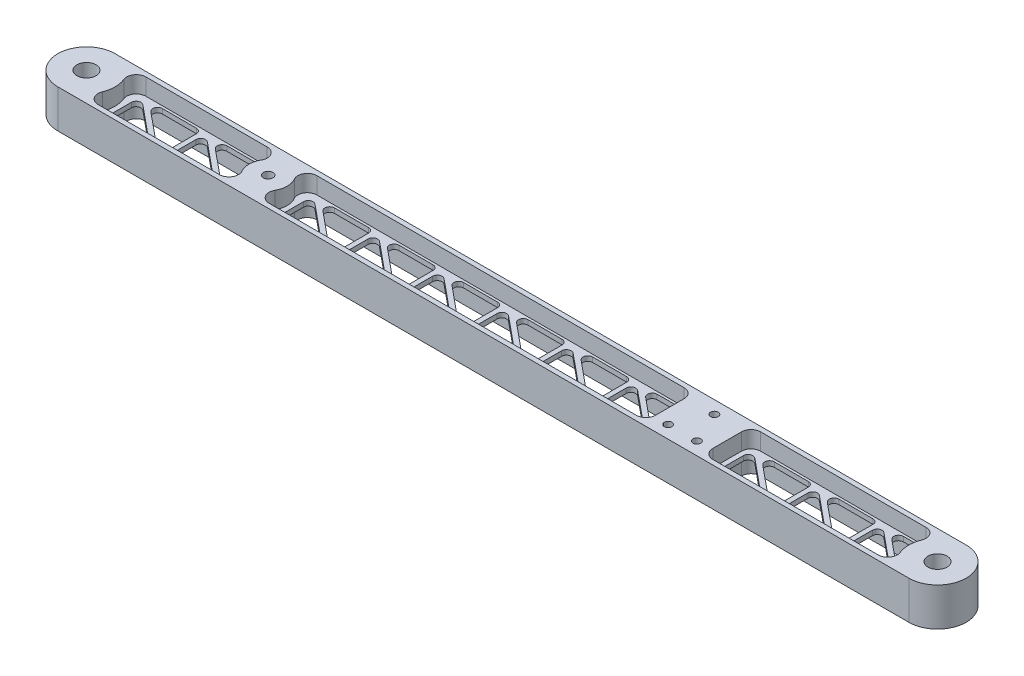
SolidWorks part; units mm, degrees
note: The reader was unsure of these and kept them because the rebuilt part matched: shared geometry of "Sketch13<4>".
material "7075-T6 (SN)"
ref_plane "Front Plane" through (0, 0, 0) normal (0, 0, 1) x (1, 0, 0)
ref_plane "Top Plane" through (0, 0, 0) normal (0, 1, 0) x (1, 0, 0)
ref_plane "Right Plane" through (0, 0, 0) normal (1, 0, 0) x (0, 0, -1)
sketch "Sketch2" plane through (0, 0, 0) normal (0, 1, 0) x (1, 0, 0)
  line L0 (0, 0) -> (120.65, 0)
  line L1 (0, 0) -> (565.15, 0)
  line L2 (0, 0) -> (0, 38.1) construction
  line L3 (0, 38.1) -> (565.15, 38.1)
  line L4 (565.15, 0) -> (565.15, 38.1) construction
  line L5 (120.65, 0) -> (120.65, 38.1) construction
  circle A0 centre (120.65, 19.05) radius 19.05
  arc A1 (565.15, 38.1) -> (565.15, 0) centre (565.15, 19.05) cw
  circle A2 centre (120.65, 19.05) radius 3.175
  circle A3 centre (565.15, 19.05) radius 6.35
  arc A4 (0, 38.1) -> (0, 0) centre (0, 19.05) ccw
  circle A5 centre (0, 19.05) radius 6.35
  dimension "D4" = 6.35
  dimension "D5" = 12.7
  dimension "D6" = 12.7
  dimension "D1" = 565.15
  dimension "D2" = 38.1
  dimension "D3" = 120.65
extrude "Boss-Extrude1" add sketch "Sketch2" along normal blind 25.4 contours A0 L3 L2 L0 | A0 A2 | A1 L3 A0 L1 A3
sketch "Sketch12" plane through (0, 0, -38.1) normal (0, 0, -1) x (-1, 0, 0)
  line L0 (-565.15, 25.4) -> (-425.45, 25.4)
  line L1 (0, 25.4) -> (-565.15, 25.4) construction
  line L2 (-387.35, 0) -> (-425.45, 0)
  line L3 (-425.45, 25.4) -> (-425.45, 0)
  line L5 (-387.35, 0) -> (-387.35, 25.4)
  line L6 (-425.45, 25.4) -> (-387.35, 25.4)
  line L7 (0, 0) -> (-565.15, 0) construction
  dimension "D1" = 139.7
  dimension "D2" = 38.1
sketch "Sketch13" plane through (0, 25.4, 0) normal (0, 1, 0) x (1, 0, 0)
  line L0 (565.15, 38.1) -> (565.15, 0) construction
  line L1 (0, 38.1) -> (0, 0) construction
  line L2 (565.15, 38.1) -> (565.15, 0) construction
  line L3 (565.15, 34.925) -> (0, 34.925)
  line L4 (0, 3.175) -> (565.15, 3.175)
  line L5 (565.15, 38.1) -> (425.45, 38.1) construction
  line L6 (0, 0) -> (565.15, 0) construction
  line L7 (19.05, 19.05) -> (22.225, 19.05) construction
  line L8 (22.225, 33.3375) -> (22.225, 4.7625)
  line L9 (22.225, 4.7625) -> (56.9185, 4.7625)
  line L10 (56.9185, 4.7625) -> (22.225, 33.3375)
  line L11 (27.219, 33.3375) -> (61.9125, 4.7625)
  line L12 (61.9125, 4.7625) -> (61.9125, 33.3375)
  line L13 (61.9125, 33.3375) -> (27.219, 33.3375)
  line L14 (65.0875, 33.3375) -> (65.0875, 4.7625)
  line L15 (65.0875, 4.7625) -> (99.781, 4.7625)
  line L16 (99.781, 4.7625) -> (65.0875, 33.3375)
  line L17 (70.0815, 33.3375) -> (104.775, 4.7625)
  line L18 (104.775, 4.7625) -> (104.775, 33.3375)
  line L19 (104.775, 33.3375) -> (70.0815, 33.3375)
  line L20 (61.9125, 19.05) -> (65.0875, 19.05) construction
  line L21 (350.8375, 33.3375) -> (350.8375, 4.7625)
  line L22 (350.8375, 4.7625) -> (384.175, 4.7625)
  line L23 (44.5658, 33.3375) -> (44.5658, 34.925) construction
  line L24 (39.5717, 4.7625) -> (39.5717, 3.175) construction
  line L25 (120.65, 34.925) -> (120.65, 3.175) construction
  line L26 (384.175, 5.8793) -> (350.8375, 33.3375)
  line L27 (355.8315, 33.3375) -> (384.175, 9.9926)
  line L28 (107.95, 19.05) -> (104.775, 19.05) construction
  line L29 (133.35, 19.05) -> (136.525, 19.05) construction
  line L30 (136.525, 33.3375) -> (136.525, 4.7625)
  line L31 (136.525, 4.7625) -> (171.2185, 4.7625)
  line L32 (171.2185, 4.7625) -> (136.525, 33.3375)
  line L33 (141.519, 33.3375) -> (176.2125, 4.7625)
  line L34 (176.2125, 4.7625) -> (176.2125, 33.3375)
  line L35 (176.2125, 33.3375) -> (141.519, 33.3375)
  line L36 (387.35, 38.1) -> (387.35, 0)
  line L37 (425.45, 38.1) -> (387.35, 38.1) construction
  line L38 (387.35, 0) -> (425.45, 0)
  line L39 (425.45, 0) -> (425.45, 38.1)
  line L40 (387.35, 38.1) -> (425.45, 38.1) construction
  line L41 (425.45, 38.1) -> (387.35, 38.1)
  line L42 (179.3875, 33.3375) -> (179.3875, 4.7625)
  line L43 (179.3875, 4.7625) -> (214.081, 4.7625)
  line L44 (214.081, 4.7625) -> (179.3875, 33.3375)
  line L45 (184.3815, 33.3375) -> (219.075, 4.7625)
  line L46 (219.075, 4.7625) -> (219.075, 33.3375)
  line L47 (219.075, 33.3375) -> (184.3815, 33.3375)
  line L48 (176.2125, 19.05) -> (179.3875, 19.05) construction
  line L49 (222.25, 33.3375) -> (222.25, 4.7625)
  line L50 (222.25, 4.7625) -> (256.9435, 4.7625)
  line L51 (256.9435, 4.7625) -> (222.25, 33.3375)
  line L52 (227.244, 33.3375) -> (261.9375, 4.7625)
  line L53 (261.9375, 4.7625) -> (261.9375, 33.3375)
  line L54 (261.9375, 33.3375) -> (227.244, 33.3375)
  line L55 (219.075, 19.05) -> (222.25, 19.05) construction
  line L56 (265.1125, 33.3375) -> (265.1125, 4.7625)
  line L57 (265.1125, 4.7625) -> (299.806, 4.7625)
  line L58 (299.806, 4.7625) -> (265.1125, 33.3375)
  line L59 (270.1065, 33.3375) -> (304.8, 4.7625)
  line L60 (304.8, 4.7625) -> (304.8, 33.3375)
  line L61 (304.8, 33.3375) -> (270.1065, 33.3375)
  line L62 (261.9375, 19.05) -> (265.1125, 19.05) construction
  line L63 (307.975, 33.3375) -> (307.975, 4.7625)
  line L64 (307.975, 4.7625) -> (342.6685, 4.7625)
  line L65 (342.6685, 4.7625) -> (307.975, 33.3375)
  line L66 (312.969, 33.3375) -> (347.6625, 4.7625)
  line L67 (347.6625, 4.7625) -> (347.6625, 33.3375)
  line L68 (347.6625, 33.3375) -> (312.969, 33.3375)
  line L69 (304.8, 19.05) -> (307.975, 19.05) construction
  line L70 (548.126, 33.3375) -> (519.344, 33.3375)
  line L71 (530.4996, 20.036) -> (532.5181, 22.4868) construction
  line L72 (546.6492, 6.7345) -> (514.35, 33.3375)
  line L73 (384.175, 5.8793) -> (384.175, 4.7625)
  line L75 (384.175, 5.8793) -> (350.8375, 33.3375)
  line L76 (384.175, 33.3375) -> (355.8315, 33.3375)
  line L77 (347.6625, 19.05) -> (350.8375, 19.05) construction
  line L78 (384.175, 33.3375) -> (384.175, 9.9926)
  line L84 (425.45, 19.05) -> (428.625, 19.05) construction
  line L85 (428.625, 33.3375) -> (428.625, 4.7625)
  line L86 (428.625, 4.7625) -> (463.3185, 4.7625)
  line L87 (463.3185, 4.7625) -> (428.625, 33.3375)
  line L88 (433.619, 33.3375) -> (468.3125, 4.7625)
  line L89 (468.3125, 4.7625) -> (468.3125, 33.3375)
  line L90 (468.3125, 33.3375) -> (433.619, 33.3375)
  line L91 (471.4875, 33.3375) -> (471.4875, 4.7625)
  line L92 (471.4875, 4.7625) -> (506.181, 4.7625)
  line L93 (506.181, 4.7625) -> (471.4875, 33.3375)
  line L94 (476.4815, 33.3375) -> (511.175, 4.7625)
  line L95 (511.175, 4.7625) -> (511.175, 33.3375)
  line L96 (511.175, 33.3375) -> (476.4815, 33.3375)
  line L97 (468.3125, 19.05) -> (471.4875, 19.05) construction
  line L98 (514.35, 33.3375) -> (514.35, 4.7625)
  line L99 (514.35, 4.7625) -> (548.126, 4.7625)
  line L101 (519.344, 33.3375) -> (543.6845, 13.2897)
  line L104 (511.175, 19.05) -> (514.35, 19.05) construction
  line L112 (387.35, 19.05) -> (425.45, 19.05) construction
  line L113 (565.15, 19.05) -> (546.1, 19.05) construction
  line L114 (546.1, 19.05) -> (546.1, 38.1) construction
  line L115 (546.1, 38.1) -> (546.1, 3.175) construction
  line L116 (406.4, 38.1) -> (406.4, 0) construction
  line L117 (396.875, 38.1) -> (396.875, 0) construction
  line L118 (415.925, 0) -> (415.925, 38.1) construction
  line L119 (387.35, 29.6333) -> (425.45, 29.6333) construction
  line L120 (387.35, 8.4667) -> (425.45, 8.4667) construction
  line L121 (568.4516, 33.3375) -> (565.15, 33.3375) [skipped]
  line L122 (554.0375, 4.7625) -> (554.0375, 33.3375) [skipped]
  line L123 (554.8268, -0.0009) -> (549.9493, 4.0164) [skipped]
  line L124 (390.525, 29.6333) -> (390.525, 33.3375) [skipped]
  circle A0 centre (565.15, 19.05) radius 19.05
  arc A1 (109.6515, 25.4) -> (109.6515, 12.7) centre (120.65, 19.05) ccw
  circle A2 centre (0, 19.05) radius 19.05
  arc A3 (104.1522, 34.925) -> (109.6515, 25.4) centre (104.1522, 28.575) cw
  arc A4 (546.6492, 6.7345) -> (548.126, 4.7625) centre (565.15, 19.05) ccw
  arc A5 (548.126, 33.3375) -> (543.6845, 13.2897) centre (565.15, 19.05) ccw
  arc A6 (109.6515, 12.7) -> (104.1522, 3.175) centre (104.1522, 9.525) cw
  arc A7 (131.6485, 12.7) -> (137.1478, 3.175) centre (137.1478, 9.525) ccw
  arc A8 (137.1478, 34.925) -> (131.6485, 25.4) centre (137.1478, 28.575) ccw
  arc A9 (131.6485, 12.7) -> (131.6485, 25.4) centre (120.65, 19.05) ccw
  point P164 (406.4, 29.6333)
  dimension "D1" = 25.4
  dimension "D9" = 3.175
  dimension "D30" = 8.4667
  dimension "D31" = 3.175
  dimension "D19" = 3.175
  dimension "D25" = 3.175
  dimension "D4" = 6.35
  dimension "D2" = 3.175
  dimension "D3" = 3.175
  dimension "Triangle Size" = 1.5875
  dimension "D6" = 3.175
  dimension "D7" = 3.175
  dimension "D10" = 3.175
  dimension "D11" = 3.175
  dimension "D14" = 3.175
  dimension "D15" = 139.7
  dimension "D16" = 38.1
  dimension "D17" = 6
  dimension "D18" = 3.175
  dimension "D20" = 3.175
  dimension "D23" = 3.175
  dimension "D26" = 3.175
  dimension "D27" = 9.525
  dimension "D28" = 9.525
  dimension "D29" = 8.4667
  dimension "D8" = 2
  dimension "D24" = 3
extrude "Cut-Extrude2" cut sketch "Sketch13" against normal up to next
extrude "Cut-Extrude3" cut sketch "Sketch13<4>" against normal blind 11.1125
sketch "Sketch13<4>" plane through (0, 25.4, 0) normal (0, 1, 0) x (1, 0, 0) same geometry as "Sketch13"
ref_plane "Plane1" through (0, 12.7, 0) normal (0, -1, 0) x (-1, 0, 0)
mirror "Mirror1" about plane through (0, 12.7, 0) normal (0, -1, 0) of "Cut-Extrude3"
fillet "Fillet1" radius 3.175 63 edges at (104.775, 12.7, -33.3375) (104.775, 12.7, -4.7625) (70.0815, 12.7, -33.3375) (99.781, 12.7, -4.7625) (65.0875, 12.7, -4.7625) (65.0875, 12.7, -33.3375) (61.9125, 12.7, -33.3375) (61.9125, 12.7, -4.7625) (27.219, 12.7, -33.3375) (56.9185, 12.7, -4.7625) (22.225, 12.7, -4.7625) (22.225, 12.7, -33.3375) (347.6625, 12.7, -33.3375) (347.6625, 12.7, -4.7625) (312.969, 12.7, -33.3375) (342.6685, 12.7, -4.7625) (307.975, 12.7, -4.7625) (307.975, 12.7, -33.3375) (304.8, 12.7, -33.3375) (304.8, 12.7, -4.7625) (270.1065, 12.7, -33.3375) (299.806, 12.7, -4.7625) (265.1125, 12.7, -4.7625) (265.1125, 12.7, -33.3375) (261.9375, 12.7, -33.3375) (261.9375, 12.7, -4.7625) (227.244, 12.7, -33.3375) (256.9435, 12.7, -4.7625) (222.25, 12.7, -4.7625) (222.25, 12.7, -33.3375) (219.075, 12.7, -33.3375) (219.075, 12.7, -4.7625) (184.3815, 12.7, -33.3375) (214.081, 12.7, -4.7625) (179.3875, 12.7, -4.7625) (179.3875, 12.7, -33.3375) (176.2125, 12.7, -33.3375) (176.2125, 12.7, -4.7625) (141.519, 12.7, -33.3375) (171.2185, 12.7, -4.7625) (136.525, 12.7, -4.7625) (136.525, 12.7, -33.3375) (514.35, 12.7, -4.7625) (511.175, 12.7, -33.3375) (511.175, 12.7, -4.7625) (476.4815, 12.7, -33.3375) (506.181, 12.7, -4.7625) (471.4875, 12.7, -4.7625) (471.4875, 12.7, -33.3375) (468.3125, 12.7, -33.3375) (468.3125, 12.7, -4.7625) (433.619, 12.7, -33.3375) (463.3185, 12.7, -4.7625) (428.625, 12.7, -4.7625) (428.625, 12.7, -33.3375) (548.126, 12.7, -33.3375) (543.6845, 12.7, -13.2897) (514.35, 12.7, -33.3375) (384.175, 12.7, -9.9926) (355.8315, 12.7, -33.3375) (384.175, 12.7, -33.3375) (350.8375, 12.7, -4.7625) (350.8375, 12.7, -33.3375)
hole_wizard "1/4-20 Tapped Hole1" positions "3DSketch1" profile "Sketch14" tap size "1/4-20" standard "ANSI Inch"
sketch3d "3DSketch1"
  line L0 (396.875, 25.4, -38.1) -> (396.875, 25.4, 0) construction
  line L1 (387.35, 25.4, -8.4667) -> (425.45, 25.4, -8.4667) construction
  line L3 (415.925, 25.4, 0) -> (415.925, 25.4, -38.1) construction
  point P0 (396.875, 25.4, -8.4667)
  point P10 (415.925, 25.4, -8.4667)
  point P14 (406.4, 25.4, -29.6333)
sketch "Sketch14" plane through (396.875, 25.4, -8.4667) normal (1, 0, 0) x (0, 0, 1)
  line L0 (0, 0) -> (0, 20.5838)
  line L1 (0, 20.5838) -> (2.5527, 19.05)
  line L2 (2.5527, 19.05) -> (2.5527, 0)
  line L5 (2.5527, 0) -> (0, 0)
  line L10 (0, 20.5838) -> (-2.5527, 19.05) construction
  line L11 (0, -6.35) -> (0, 107.95) construction
  dimension "Tap Drill Dia." = 5.1054
  dimension "Tap Drill Depth" = 19.05
  dimension "Drill Angle" = 118
cosmetic thread "Hole Thread1" parameters "D1"=12.7, "D2"=6.35
cosmetic thread "Hole Thread2" parameters "D1"=12.7, "D2"=6.35
cosmetic thread "Hole Thread4" parameters "D1"=12.7, "D2"=6.35
fillet "Fillet3" radius 3.175 4 edges at (547.3602, 14.2875, -5.728) (546.6492, 12.7, -6.7345) (548.126, 12.7, -4.7625) (547.3602, 11.1125, -5.728)
fillet "Fillet4" radius 3.175 1 edges at (519.344, 12.7, -33.3375)
fillet "Fillet5" radius 6.35 16 edges at (554.6197, 19.8438, -3.175) (554.6197, 19.8438, -34.925) (425.45, 19.8438, -3.175) (425.45, 19.8438, -34.925) (387.35, 19.8438, -3.175) (387.35, 19.8438, -34.925) (10.5303, 19.8438, -34.925) (10.5303, 19.8438, -3.175) (10.5303, 5.5562, -3.175) (10.5303, 5.5562, -34.925) (387.35, 5.5562, -34.925) (387.35, 5.5562, -3.175) (554.6197, 5.5562, -34.925) (554.6197, 5.5562, -3.175) (425.45, 5.5562, -3.175) (425.45, 5.5562, -34.925)
fillet "Fillet6" radius 3.175 4 edges at (384.175, 14.2875, -5.3209) (384.175, 12.7, -5.8793) (384.175, 12.7, -4.7625) (384.175, 11.1125, -5.3209)
